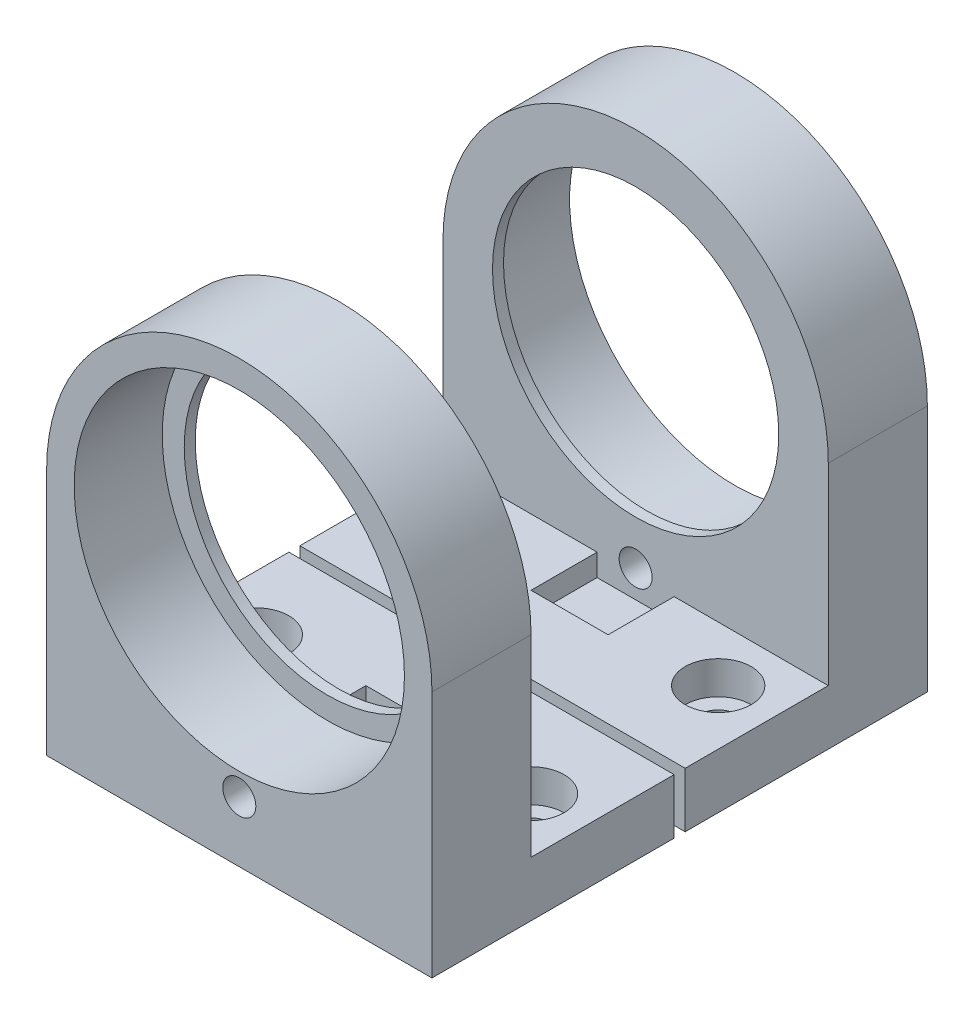
SolidWorks part; units mm, degrees
other "标注1"
sketch "草图5" plane through (-20, 40, 22.5) normal (-0.1295, 0.131, 0.9829) x (0.9907, 0.0594, 0.1226)
other "标注2"
sketch "草图13" plane through (-17.5, 0, -22.5) normal (-0.0964, -0.0078, -0.9953) x (0.9949, 0.0275, -0.0965)
other "标注3"
sketch "草图14" plane through (-17.5, 0, -22.5) normal (-0.0964, -0.0078, -0.9953) x (0.9949, 0.0275, -0.0965)
ref_plane "前视基准面" through (0, 0, 0) normal (0, 0, 1) x (1, 0, 0)
ref_plane "上视基准面" through (0, 0, 0) normal (0, 1, 0) x (1, 0, 0)
ref_plane "右视基准面" through (0, 0, 0) normal (1, 0, 0) x (0, 0, -1)
sketch "草图1" plane through (0, 0, 0) normal (1, 0, 0) x (0, 0, -1)
  line L0 (22.5, 0) -> (-22.5, 0)
  line L1 (-22.5, 0) -> (-22.5, 40)
  line L2 (-22.5, 40) -> (-13.5, 40)
  line L3 (-13.5, 40) -> (-13.5, 5)
  line L4 (-13.5, 5) -> (13.5, 5)
  line L5 (0, 5) -> (0, 0) construction
  line L6 (13.5, 40) -> (13.5, 5)
  line L7 (22.5, 40) -> (13.5, 40)
  line L8 (22.5, 0) -> (22.5, 40)
  dimension "D1" = 45
  dimension "D2" = 40
  dimension "D3" = 5
  dimension "D4" = 27
extrude "凸台-拉伸1" add sketch "草图1" along normal mid plane 35
sketch "草图2" plane through (0, 0, 22.5) normal (0, 0, 1) x (1, 0, 0)
  line L0 (17.5, 40) -> (17.5, 0) construction
  line L1 (17.5, 40) -> (-17.5, 40) construction
  line L2 (-17.5, 40) -> (-17.5, 0) construction
  line L3 (17.5, 40) -> (17.5, 10.3175)
  line L4 (17.5, 40) -> (-17.5, 40)
  line L5 (-17.5, 40) -> (-17.5, 22.5)
  arc A1 (17.5, 22.5) -> (-17.5, 22.5) centre (0, 22.5) ccw
  line M2 (-17.5, 40) -> (-17.5, 0)
  line M5 (17.5, 40) -> (-17.5, 40)
  dimension "D1" = 35
extrude "切除-拉伸1" cut sketch "草图2" against normal through all both and the other way through all contours A1 L4 M2 | A1 L3 M5 region at (-13.5911, 36.0911, 22.5) region at (13.5911, 36.0911, 22.5)
sketch "草图6" plane through (0, 5, 0) normal (0, 1, 0) x (1, 0, 0)
  line L0 (-17.5, 0) -> (17.5, 0) construction
  line L1 (-17.5, 13.5) -> (-17.5, -13.5) construction
  line L2 (17.5, 13.5) -> (17.5, -13.5) construction
  line L3 (0, 13.5) -> (0, -13.5) construction
  line L4 (17.5, 13.5) -> (-17.5, 13.5) construction
  line L5 (17.5, -13.5) -> (-17.5, -13.5) construction
  circle A0 centre (-12.5, 8.5) radius 1.55
  circle A1 centre (12.5, 8.5) radius 1.55
  circle A2 centre (12.5, -8.5) radius 1.55
  circle A3 centre (-12.5, -8.5) radius 1.55
  dimension "D1" = 3.1
  dimension "D2" = 5
  dimension "D3" = 5
extrude "切除-拉伸4" cut sketch "草图6" against normal through all
sketch "草图7" plane through (0, 0, 22.5) normal (0, 0, 1) x (1, 0, 0)
  circle A0 centre (0, 22.5) radius 15
  dimension "D1" = 30
extrude "切除-拉伸5" cut sketch "草图7" against normal blind 8
sketch "草图8" plane through (0, 0, 14.5) normal (0, 0, 1) x (1, 0, 0)
  circle A0 centre (0, 22.5) radius 13
  dimension "D1" = 26
extrude "切除-拉伸6" cut sketch "草图8" against normal blind 2
mirror "镜向1" about plane through (0, 0, 0) normal (0, 0, 1) of "切除-拉伸5", "切除-拉伸6"
sketch "草图9" plane through (0, 0, -22.5) normal (0, 0, -1) x (-1, 0, 0)
  line L0 (-17.5, 0) -> (-17.5, 22.5) construction
  circle A0 centre (0, 5.5) radius 1.5
  circle A1 centre (0, 22.5) radius 15 construction
  dimension "D1" = 17.5
  dimension "D2" = 17
extrude "切除-拉伸7" cut sketch "草图9" against normal blind 14
sketch "草图10" plane through (0, 5, 0) normal (0, 1, 0) x (1, 0, 0)
  line L0 (-1.4142, 13.5) -> (-17.5, 13.5) construction
  line L1 (-3.5, 13.5) -> (3.5, 13.5)
  line L2 (-3.5, 13.5) -> (-3.5, 7.5)
  line L3 (-3.5, 7.5) -> (3.5, 7.5)
  line L4 (3.5, 13.5) -> (3.5, 7.5)
  line L6 (17.5, 13.5) -> (17.5, -13.5) construction
  line L7 (-17.5, 13.5) -> (-17.5, -13.5) construction
  dimension "D1" = 14
  dimension "D2" = 14
extrude "切除-拉伸8" cut sketch "草图10" against normal blind 2
mirror "镜向2" about plane through (0, 0, 0) normal (0, 0, 1) of "切除-拉伸8", "切除-拉伸7"
sketch "草图15" plane through (0, 5, 0) normal (0, 1, 0) x (1, 0, 0)
  line L0 (-17.5, 0) -> (17.5, 0) construction
  line L1 (-17.5, 13.5) -> (-17.5, -13.5) construction
  line L2 (17.5, 13.5) -> (17.5, -13.5) construction
  line L4 (-17.5, 0.5) -> (17.5, 0.5)
  line L5 (-17.5, 0.5) -> (-17.5, -0.5)
  line L6 (-17.5, -0.5) -> (17.5, -0.5)
  line L7 (17.5, 0.5) -> (17.5, -0.5)
  dimension "D1" = 1
  dimension "D2" = 0.5
extrude "切除-拉伸9" cut sketch "草图15" against normal blind 10
sketch "草图16" plane through (0, 5, 0) normal (0, 1, 0) x (1, 0, 0)
  circle A0 centre (-12.5, 8.5) radius 3
  circle A1 centre (12.5, 8.5) radius 3
  circle A2 centre (12.5, -8.5) radius 3
  circle A3 centre (-12.5, -8.5) radius 3
  dimension "D1" = 6
extrude "切除-拉伸10" cut sketch "草图16" against normal blind 3
